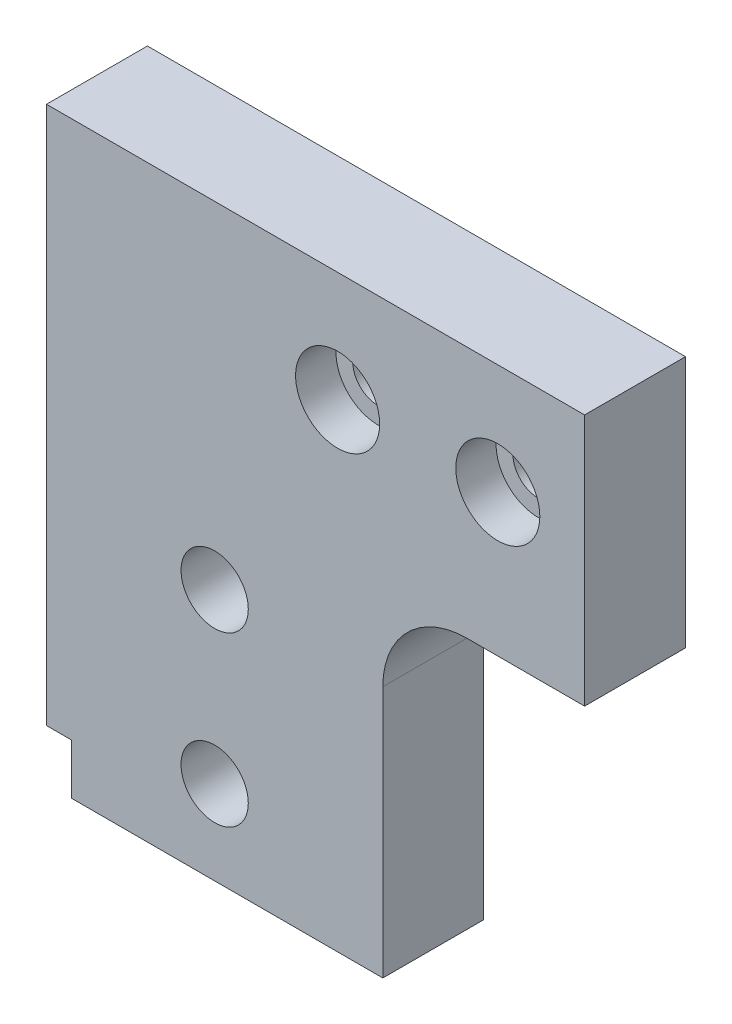
SolidWorks part; units mm, degrees
ref_plane "Plano frontal" through (0, 0, 0) normal (0, 0, 1) x (1, 0, 0)
ref_plane "Plano superior" through (0, 0, 0) normal (0, 1, 0) x (1, 0, 0)
ref_plane "Plano direito" through (0, 0, 0) normal (1, 0, 0) x (0, 0, -1)
sketch "Esboço1" plane through (0, 0, 0) normal (0, 0, 1) x (1, 0, 0)
  line L1 (-16, 17.5) -> (16, 17.5)
  line L2 (-16, 17.5) -> (-16, -17.5)
  line L3 (-16, -17.5) -> (16, -17.5)
  line L4 (16, 17.5) -> (16, -17.5)
  line L5 (-16, 17.5) -> (16, -17.5) construction
  line L6 (-16, -17.5) -> (16, 17.5) construction
  point P0 (0, 0)
  dimension "D1" = 32
  dimension "D2" = 35
extrude "Ressalto-extrusão1" add sketch "Esboço1" along normal blind 6
sketch "Esboço2" plane through (0, 0, 6) normal (0, 0, 1) x (1, 0, 0)
  line L1 (16, -17.5) -> (4, -17.5)
  line L2 (16, -17.5) -> (16, 2.5)
  line L3 (16, 2.5) -> (4, 2.5)
  line L4 (4, -17.5) -> (4, 2.5)
  line L5 (-16, -17.5) -> (16, -17.5) construction
  line L6 (-6, 17.5) -> (-6, -17.5)
  line L7 (-6, 17.5) -> (-6, -17.5) construction
  line L8 (16, 17.5) -> (-16, 17.5) construction
  circle A0 centre (-6, -12.5) radius 2
  circle A1 centre (-6, -2.5) radius 2
  dimension "D4" = 4
  dimension "D1" = 12
  dimension "D2" = 15
  dimension "D5" = 5
  dimension "D6" = 10
  dimension "D3" = 10
extrude "Corte-extrusão1" cut sketch "Esboço2" against normal up to surface (6 mm away) up to face at (0, 0, 0)
fillet "Filete1" radius 5 1 edges at (4, 2.5, 3)
sketch "Esboço5" plane through (0, 0, 0) normal (0, 0, -1) x (-1, 0, 0)
  circle A0 centre (-10.8375, 10.9375) radius 1.175 construction
  circle A1 centre (-1.3125, 10.9375) radius 1.175 construction
  circle A2 centre (-10.8375, 10.9375) radius 1.175 construction
  circle A3 centre (-1.3125, 10.9375) radius 1.175 construction
  circle A4 centre (-10.8375, 10.9375) radius 1.5
  circle A5 centre (-1.3125, 10.9375) radius 1.5
  dimension "D1" = 3
extrude "Corte-extrusão3" cut sketch "Esboço5" against normal up to surface (6 mm away) up to face at (2.2806, 0.5051, 6)
sketch "Esboço6" plane through (0, 0, 6) normal (0, 0, 1) x (1, 0, 0)
  circle A0 centre (10.8375, 10.9375) radius 2.5
  circle A1 centre (1.3125, 10.9375) radius 2.5
  dimension "D1" = 5
extrude "Corte-extrusão4" cut sketch "Esboço6" against normal blind 2.4
sketch "Esboço7" plane through (0, 0, 6) normal (0, 0, 1) x (1, 0, 0)
  line L1 (-16, -17.5) -> (-14.5, -17.5)
  line L2 (-16, -17.5) -> (-16, -14.5)
  line L3 (-16, -14.5) -> (-14.5, -14.5)
  line L4 (-14.5, -17.5) -> (-14.5, -14.5)
  dimension "D1" = 1.5
  dimension "D2" = 3
extrude "Corte-extrusão5" cut sketch "Esboço7" against normal up to surface (6 mm away) up to face at (9.3375, 10.9375, 0)
